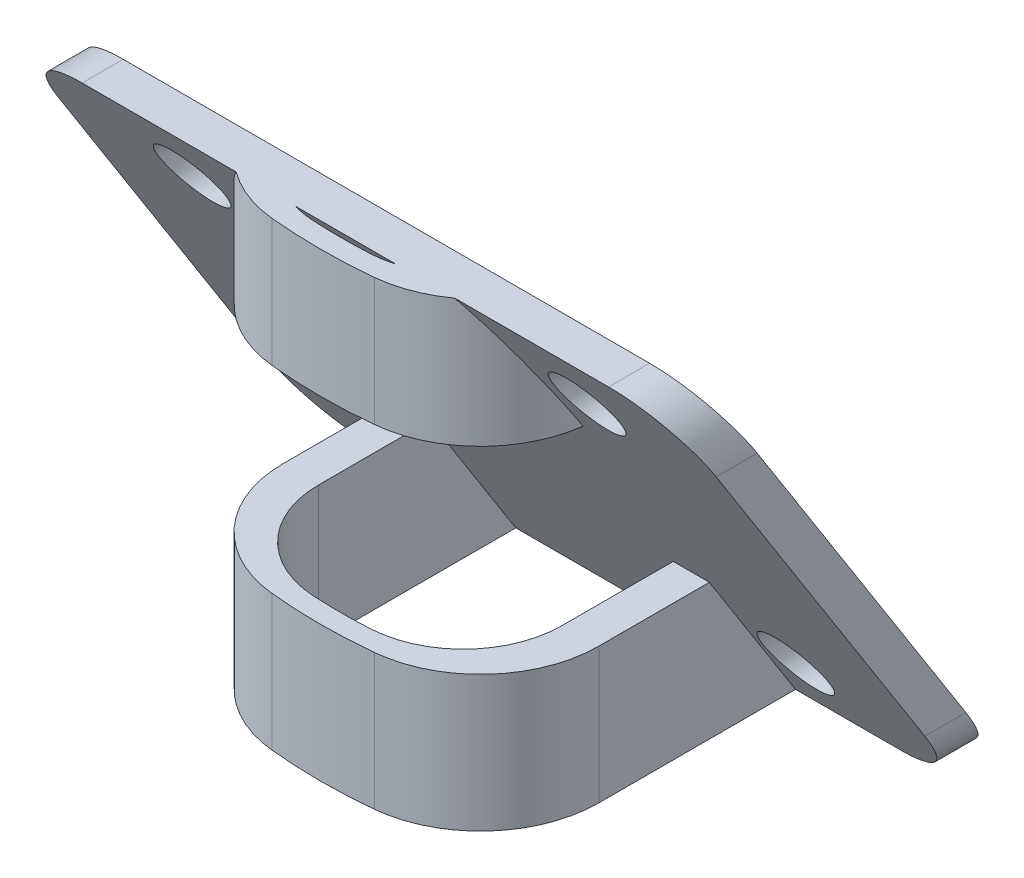
SolidWorks part; units mm, degrees
ref_plane "Front Plane" through (0, 0, 0) normal (0, 0, 1) x (1, 0, 0)
ref_plane "Top Plane" through (0, 0, 0) normal (0, 1, 0) x (1, 0, 0)
ref_plane "Right Plane" through (0, 0, 0) normal (1, 0, 0) x (0, 0, -1)
sketch "Sketch1" plane through (0, 0, 0) normal (1, 0, 0) x (0, 0, -1)
  line L2 (9.3196, -5.4228) -> (-6.4019, 19.3633)
  line L5 (29.951, -37.9497) -> (9.3196, -5.4228)
  line L10 (29.951, -37.9497) -> (37.9982, -50.6367)
  line L11 (37.9982, -50.6367) -> (44.2357, -50.6367)
  line L14 (-0.1644, 19.3633) -> (-6.4019, 19.3633)
  line L15 (-0.1644, 19.3633) -> (44.2357, -50.6367)
extrude "Boss-Extrude1" add sketch "Sketch1" along normal blind 100
sketch "Sketch2" plane through (0, 0, -44.2357) normal (0, 0, -1) x (-1, 0, 0)
  circle A0 centre (-80, -41.2364) radius 5
  circle A1 centre (-20, -41.2364) radius 5
  circle A2 centre (-20, 8.7636) radius 5
  circle A3 centre (-80, 8.7636) radius 5
  dimension "D1" = 60
  dimension "D2" = 50
  dimension "D3" = 60
extrude "Cut-Extrude1" cut sketch "Sketch2" against normal blind 61
sketch "Sketch3" plane through (0, 19.3633, 0) normal (0, 1, 0) x (1, 0, 0)
  line L0 (100, -6.4019) -> (0, -6.4019) construction
  line L1 (100, -0.1644) -> (0, -0.1644) construction
  line L5 (0, -0.1644) -> (0, -6.4019)
  line L6 (0, -6.4019) -> (100, -6.4019)
  line L7 (100, -6.4019) -> (100, -0.1644)
  line L8 (100, -0.1644) -> (0, -0.1644)
  line L10 (26, -6.4019) -> (74, -6.4019)
  arc A0 (74, -6.4019) -> (26, -6.4019) centre (50, 68.2616) cw
  point P3 (50, -10.1644)
  dimension "D1" = 10
  dimension "D3" = 26
  dimension "D4" = 26
  dimension "D2" = 0
extrude "Boss-Extrude3" add sketch "Sketch3" against normal blind 70 separate body
sketch "Sketch4" plane through (0, 0, 6.4019) normal (0, 0, -1) x (-1, 0, 0)
  line L1 (-74, 19.3633) -> (-26, 19.3633)
  line L2 (-74, 19.3633) -> (-74, -50.6367)
  line L3 (-74, -50.6367) -> (-26, -50.6367)
  line L4 (-26, 19.3633) -> (-26, -50.6367)
extrude "Boss-Extrude4" add sketch "Sketch4" along normal up to surface up to face at (80, 3.7636, -3.4928)
sketch "Sketch5" plane through (0, -50.6367, 0) normal (0, -1, 0) x (1, 0, 0)
  line L0 (68.504, -37.9982) -> (31.496, -37.9982)
  line L1 (31.496, -37.9982) -> (31.496, 4.7796)
  line L2 (68.504, -37.9982) -> (68.504, 4.7796)
  line L3 (74, -37.9982) -> (74, 6.4019) construction
  line L4 (26, -37.9982) -> (26, 6.4019) construction
  line L5 (26, -37.9982) -> (0, -37.9982) construction
  arc A0 (68.504, 4.7796) -> (31.496, 4.7796) centre (50, -68.2616) ccw
  arc A1 (74, 6.4019) -> (26, 6.4019) centre (50, -68.2616) ccw construction
extrude "Cut-Extrude2" cut sketch "Sketch5" against normal up to surface up to face at (80, -46.2364, -35.2072)
fillet "Fillet1" radius 10 4 edges at (0, -50.6367, -41.117) (100, -50.6367, -41.117) (0, 19.3633, 3.2832) (100, 19.3633, 3.2832)
sketch "Sketch7" plane through (74, 0, 0) normal (1, 0, 0) x (0, 0, -1)
  line L0 (5.88, 0) -> (-34.0291, 0)
  line L1 (-6.4019, 19.3633) -> (37.9982, -50.6367) construction
  line L2 (-34.0291, 0) -> (-34.0291, -30)
  line L3 (-34.0291, -30) -> (24.9086, -30)
  line L4 (24.9086, -30) -> (5.88, 0)
  line L5 (-4.7796, -50.6367) -> (37.9982, -50.6367) construction
  line L6 (-6.4019, 19.3633) -> (-10.1644, 19.3633) construction
  dimension "D1" = 30
  dimension "D2" = 20.6367
  dimension "D3" = 19.3633
extrude "Cut-Extrude3" cut sketch "Sketch7" against normal blind 56
fillet "Fillet3" radius 18 4 edges at (74, 9.6817, 6.4019) (74, -40.3183, 6.4019) (26, -40.3183, 6.4019) (26, 9.6817, 6.4019)
fillet "Fillet4" radius 15 2 edges at (68.504, -40.3183, 4.7796) (31.496, -40.3183, 4.7796)
fillet "Fillet5" radius 15 2 edges at (68.504, 8.4028, 4.7796) (31.496, 8.4028, 4.7796)
